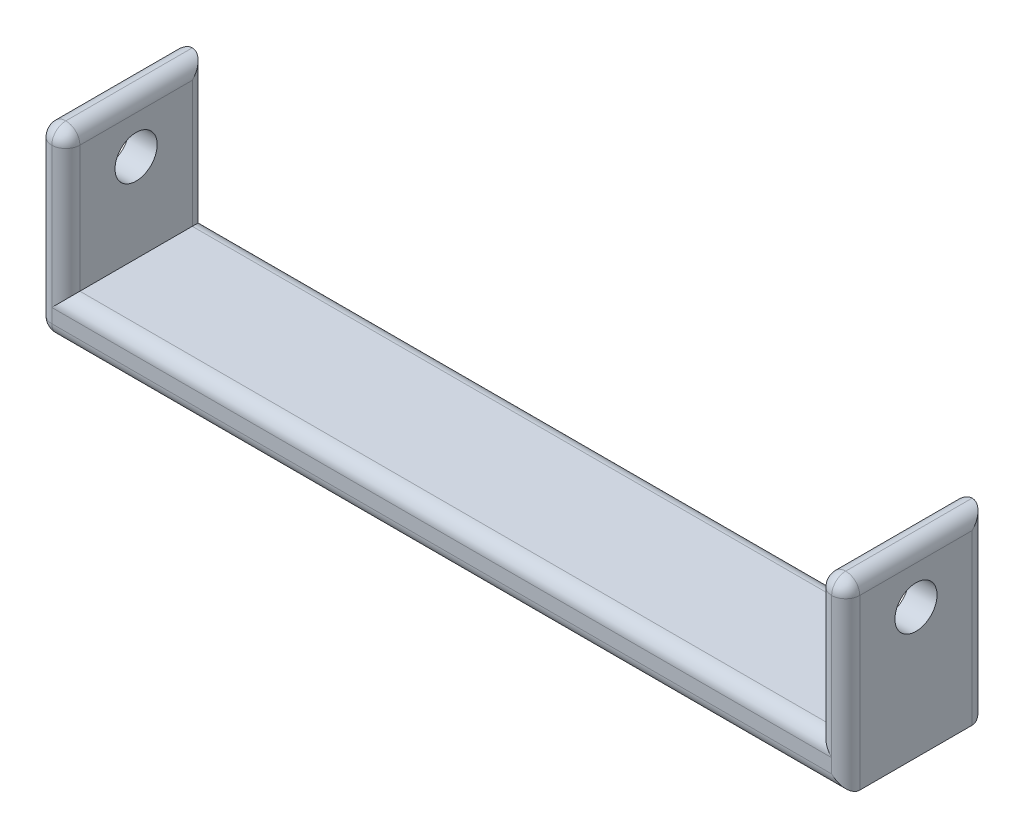
SolidWorks part; units mm, degrees
material "ABS"
ref_plane "Front Plane" through (0, 0, 0) normal (0, 0, 1) x (1, 0, 0)
ref_plane "Top Plane" through (0, 0, 0) normal (0, 1, 0) x (1, 0, 0)
ref_plane "Right Plane" through (0, 0, 0) normal (1, 0, 0) x (0, 0, -1)
sketch "Sketch1" plane through (0, 0, 0) normal (0, 1, 0) x (1, 0, 0)
  line L1 (-28.75, 5) -> (28.75, 5)
  line L2 (-28.75, 5) -> (-28.75, -5)
  line L3 (-28.75, -5) -> (28.75, -5)
  line L4 (28.75, 5) -> (28.75, -5)
  line L5 (-28.75, 5) -> (28.75, -5) construction
  line L6 (-28.75, -5) -> (28.75, 5) construction
  point P0 (0, 0)
  dimension "D1" = 57.5
  dimension "D2" = 10
extrude "Boss-Extrude1" add sketch "Sketch1" along normal blind 3
sketch "Sketch2" plane through (0, 3, 0) normal (0, 1, 0) x (1, 0, 0)
  line L0 (-28.75, 5) -> (-26.75, 5)
  line L1 (28.75, 5) -> (-28.75, 5) construction
  line L2 (-26.75, 5) -> (-26.75, -5)
  line L3 (-28.75, -5) -> (28.75, -5) construction
  line L4 (-26.75, -5) -> (-28.75, -5)
  line L5 (-28.75, -5) -> (-28.75, 5)
  line L6 (28.75, 5) -> (26.75, 5)
  line L7 (26.75, 5) -> (26.75, -5)
  line L8 (26.75, -5) -> (28.75, -5)
  line L9 (28.75, -5) -> (28.75, 5)
  dimension "D1" = 2
extrude "Boss-Extrude2" add sketch "Sketch2" along normal blind 10
sketch "Sketch3" plane through (-28.75, 0, 0) normal (-1, 0, 0) x (0, 0, 1)
  circle A0 centre (0, 9.2874) radius 1.5
extrude "Cut-Extrude1" cut sketch "Sketch3" against normal through all contours A0
fillet "Fillet1" radius 1 17 edges at (-28.75, 6.5, 5) (-26.75, 8, 5) (0, 3, 5) (26.75, 8, 5) (28.75, 6.5, 5) (0, 0, 5) (0, 3, -5) (-26.75, 13, 0) (-28.75, 13, 0) (28.75, 13, 0) (26.75, 13, 0) (26.75, 8, -5) (28.75, 6.5, -5) (-28.75, 0, 0) (-26.75, 8, -5) (-28.75, 6.5, -5) (0, 0, -5)
